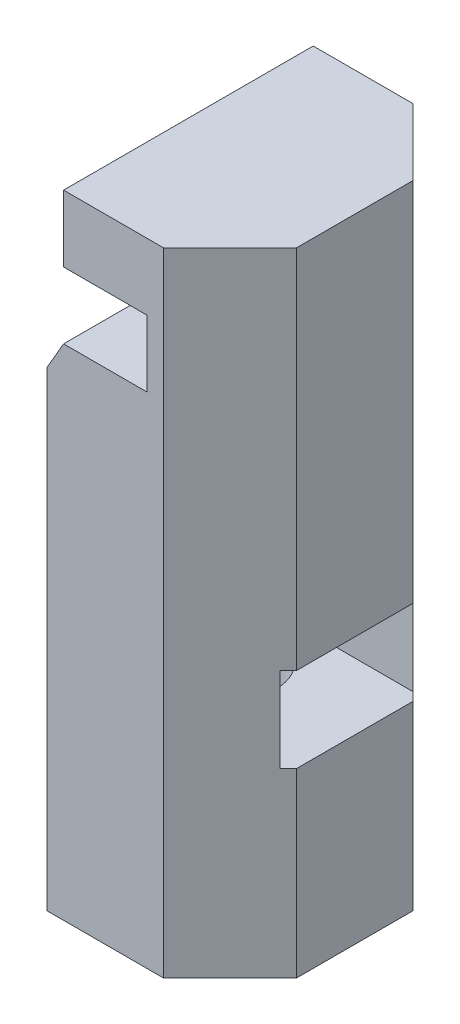
SolidWorks part; units mm, degrees
ref_plane "Front Plane" through (0, 0, 0) normal (0, 0, 1) x (1, 0, 0)
ref_plane "Top Plane" through (0, 0, 0) normal (0, 1, 0) x (1, 0, 0)
ref_plane "Right Plane" through (0, 0, 0) normal (1, 0, 0) x (0, 0, -1)
sketch "Sketch1" plane through (0, 0, 0) normal (0, 0, 1) x (1, 0, 0)
  line L0 (-6, 8) -> (4, 8)
  line L1 (4, 8) -> (4, -30)
  line L2 (4, -30) -> (-11, -30)
  line L3 (-11, -30) -> (-11, 0)
  line L5 (-11, 0) -> (-1, 0)
  line L6 (-1, 0) -> (-1, 4)
  line L8 (-1, 4) -> (-6, 4)
  line L9 (-6, 4) -> (-6, 8)
  line L10 (0, -8.25) -> (0, 8.25) construction
  line L11 (8.25, 0) -> (-8.25, 0) construction
  dimension "D1" = 5
  dimension "D2" = 10
  dimension "D3" = 4
  dimension "D4" = 15
  dimension "D5" = 30
  dimension "D6" = 4
  dimension "D7" = 4
extrude "Boss-Extrude1" add sketch "Sketch1" along normal mid plane 15
sketch "Sketch2" plane through (0, -30, 0) normal (0, -1, 0) x (1, 0, 0)
  line L0 (8.25, 0) -> (-8.25, 0) construction
  line L1 (-11, 7.5) -> (-11, -7.5) construction
  circle A0 centre (-3.5, 0) radius 5.25
  dimension "D1" = 10.5
  dimension "D2" = 7.5
extrude "Cut-Extrude1" cut sketch "Sketch2" against normal blind 6
sketch "Sketch4" plane through (0, -30, 0) normal (0, -1, 0) x (1, 0, 0)
  circle A0 centre (-3.5, 0) radius 2.75
  dimension "D1" = 5.5
extrude "Cut-Extrude3" cut sketch "Sketch4" against normal blind 28
sketch "Sketch5" plane through (4, 0, 0) normal (1, 0, 0) x (0, 0, -1)
  line L0 (0, 8.25) -> (0, -8.25) construction
  line L1 (-4, -14) -> (4, -14)
  line L2 (-4, -14) -> (-4, -19.1)
  line L3 (-4, -19.1) -> (4, -19.1)
  line L4 (4, -14) -> (4, -19.1)
  line L5 (8.25, 0) -> (-8.25, 0) construction
  dimension "D1" = 8
  dimension "D2" = 4
  dimension "D3" = 5.1
  dimension "D4" = 14
extrude "Cut-Extrude4" cut sketch "Sketch5" against normal up to next
chamfer "Chamfer2" distance 5 angle 60 1 edges at (-11, 0, 0) first distance on face at (-6, 0, 0)
chamfer "Chamfer3" distance 4 angle 45 4 edges at (-11, -19.3301, 7.5) (-11, -19.3301, -7.5) (4, -11, -7.5) (4, -11, 7.5)
